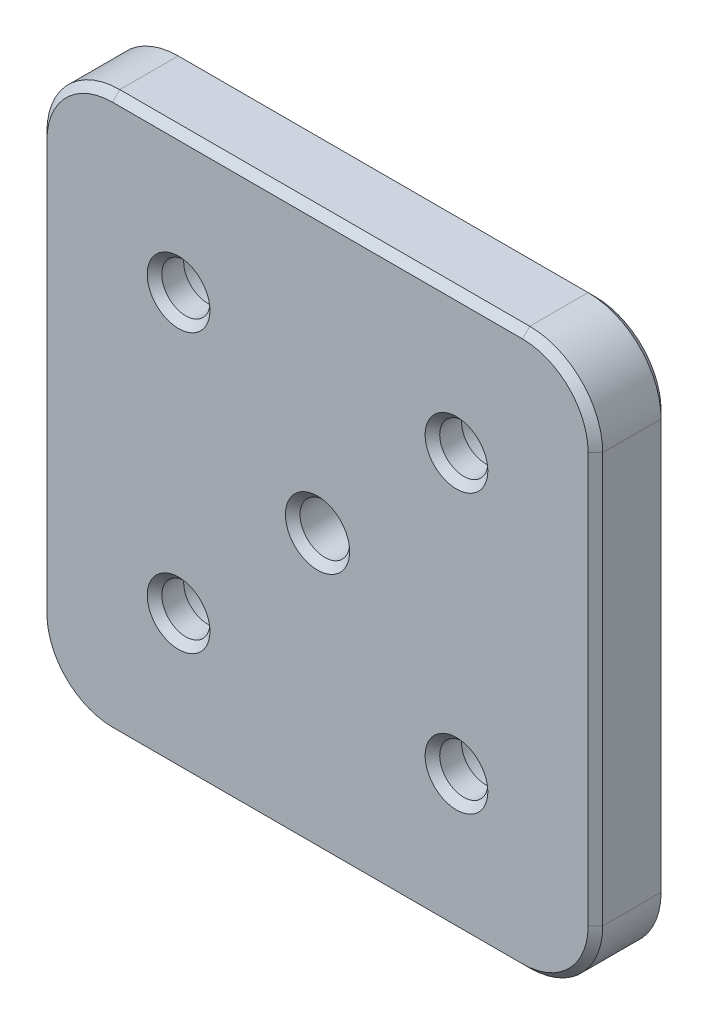
SolidWorks part; units mm, degrees
ref_plane "Front Plane" through (0, 0, 0) normal (0, 0, 1) x (1, 0, 0)
ref_plane "Top Plane" through (0, 0, 0) normal (0, 1, 0) x (1, 0, 0)
ref_plane "Right Plane" through (0, 0, 0) normal (1, 0, 0) x (0, 0, -1)
sketch "Sketch1" plane through (0, 0, 0) normal (0, 0, 1) x (1, 0, 0)
  circle A0 centre (0, 0) radius 7.5
sketch "Sketch3" plane through (0, 0, 0) normal (0, 0, 1) x (1, 0, 0)
  line L1 (-38.1, 38.1) -> (38.1, 38.1)
  line L2 (-38.1, 38.1) -> (-38.1, -38.1)
  line L3 (-38.1, -38.1) -> (38.1, -38.1)
  line L4 (38.1, 38.1) -> (38.1, -38.1)
  line L5 (-38.1, 38.1) -> (38.1, -38.1) construction
  line L6 (-38.1, -38.1) -> (38.1, 38.1) construction
  point P0 (0, 0)
extrude "Boss-Extrude3" add sketch "Sketch3" along normal blind 10
sketch "Sketch2" plane through (0, 0, 0) normal (0, 0, -1) x (-1, 0, 0)
  circle A0 centre (0, 0) radius 10
sketch "Sketch4" plane through (0, 0, 0) normal (0, 0, 1) x (1, 0, 0)
  circle A0 centre (19.05, 19.05) radius 4
  circle A1 centre (-19.05, 19.05) radius 4
  circle A2 centre (-19.05, -19.05) radius 4
  circle A3 centre (19.05, -19.05) radius 4
  dimension "D1" = 2
  dimension "D2" = 2
hole_wizard "CBORE for M6 Hex Socket Head Cap1" positions "Sketch7" profile "Sketch8" counterbore size "M6" standard "BSI" end condition through all
sketch "Sketch7" plane through (0, 0, 0) normal (0, 0, -1) x (-1, 0, 0)
  point P0 (19.05, 19.05)
  point P3 (19.05, -19.05)
  point P6 (-19.05, 19.05)
  point P9 (-19.05, -19.05)
sketch "Sketch8" plane through (-19.05, 19.05, 0) normal (1, 0, 0) x (0, 1, 0)
  line L0 (0, 0) -> (0, 10)
  line L1 (0, 10) -> (3.3, 10)
  line L3 (3.3, 10) -> (3.3, 6)
  line L4 (3.3, 6) -> (5.5, 6)
  line L5 (5.5, 6) -> (5.5, 0)
  line L7 (5.5, 0) -> (0, 0)
  line L11 (0, -6.35) -> (0, 107.95) construction
  dimension "Thru Hole Dia." = 6.6
  dimension "Thru Hole Depth" = 10
  dimension "C'Bore Dia." = 11
  dimension "C'Bore Depth" = 6
fillet "Fillet1" radius 10 4 edges at (38.1, 38.1, 5) (38.1, -38.1, 5) (-38.1, -38.1, 5) (-38.1, 38.1, 5)
extrude "Boss-Extrude4" add sketch "Sketch2" along normal blind 10
sketch "Sketch9" plane through (0, 0, -10) normal (0, 0, -1) x (-1, 0, 0)
  circle A0 centre (0, 0) radius 3.4
extrude "Cut-Extrude1" cut sketch "Sketch9" against normal through all
chamfer "Chamfer1" distance 1 angle 45 27 edges at (35.1711, -35.1711, 10) (0, -38.1, 10) (-35.1711, -35.1711, 10) (-38.1, 0, 10) (-35.1711, 35.1711, 10) (0, 38.1, 10) (35.1711, 35.1711, 10) (38.1, 0, 10) (15.75, -19.05, 10) (15.75, 19.05, 10) (-22.35, -19.05, 10) (-22.35, 19.05, 10) (-3.4, 0, 10) (-3.4, 0, -10) (-10, 0, -10) (13.55, 19.05, 0) (13.55, -19.05, 0) (-24.55, -19.05, 0) (-24.55, 19.05, 0) (38.1, 0, 0) (35.1711, 35.1711, 0) (35.1711, -35.1711, 0) (0, 38.1, 0) (0, -38.1, 0) (-35.1711, 35.1711, 0) (-35.1711, -35.1711, 0) (-38.1, 0, 0)
sketch "Sketch10" plane through (0, 0, 0) normal (0, 0, -1) x (-1, 0, 0)
  line L0 (38.1, 28.1) -> (38.1, -28.1) construction
  line L1 (28.1, -38.1) -> (-28.1, -38.1) construction
  line L2 (38.1, 28.1) -> (38.1, -28.1)
  line L3 (28.1, -38.1) -> (-28.1, -38.1)
  line L4 (28.1, -38.1) -> (38.1, -38.1)
  line L5 (38.1, -28.1) -> (38.1, -38.1)
